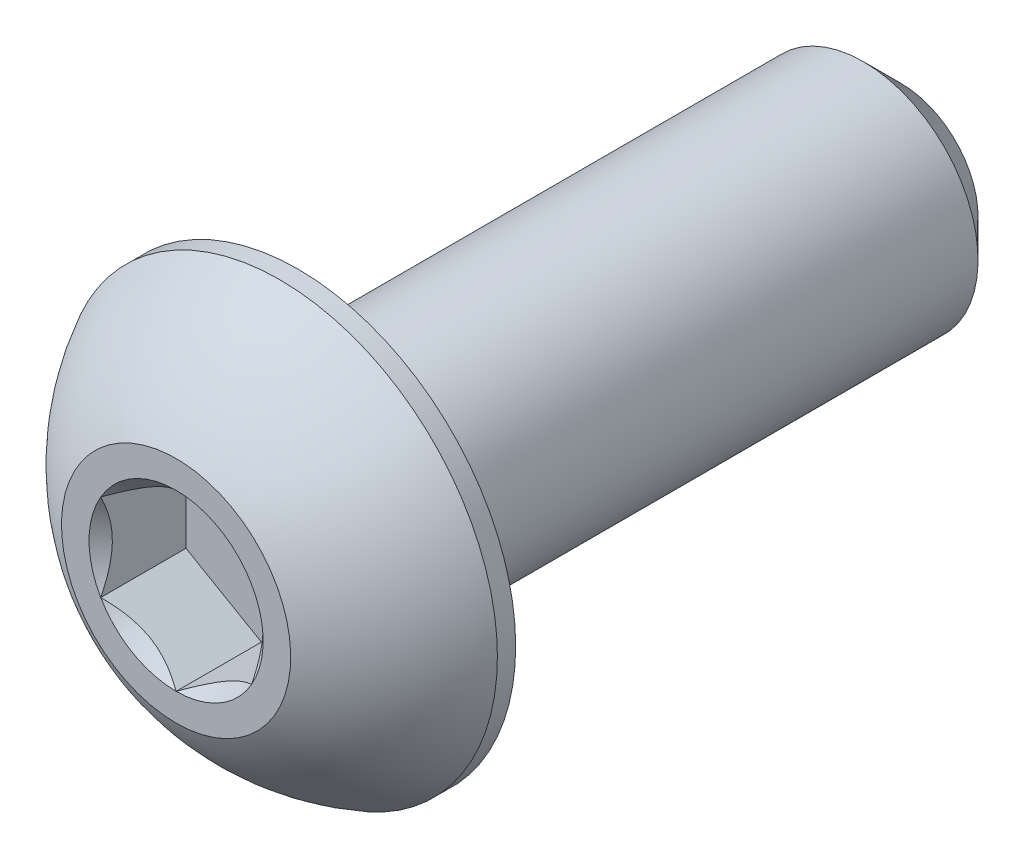
SolidWorks part; units mm, degrees
ref_plane "Front" through (0, 0, 0) normal (0, 0, 1) x (1, 0, 0)
ref_plane "Top" through (0, 0, 0) normal (0, 1, 0) x (1, 0, 0)
ref_plane "Right" through (0, 0, 0) normal (1, 0, 0) x (0, 0, -1)
sketch "Sketch1" plane through (0, 0, 0) normal (1, 0, 0) x (0, 0, -1)
  line L2 (2.5654, 2.413) -> (15.2654, 2.413)
  line L3 (15.2654, 2.413) -> (15.2654, 0)
  line L4 (15.2654, 0) -> (2.5654, 0)
  line L6 (2.1806, 4.5847) -> (2.5654, 4.5847) construction
  line L7 (15.2654, 2.413) -> (15.2654, -2.413) construction
  line L8 (0, 0) -> (2.5654, 0) construction
  line L9 (2.5654, 4.5847) -> (2.5654, -4.5847) construction
  line L11 (2.5654, 2.413) -> (2.5654, 0)
  line L13 (0, 1.5875) -> (0, -1.5875) construction
  line L14 (0, 1.5875) -> (0, 2.413) construction
  arc A3 (0, 2.413) -> (2.1806, 4.5847) centre (4.5749, 0) cw construction
  dimension "D1" = 0.3848
revolve "Revolve1" add sketch "Sketch1" angle 360 mid plane about L4
sketch "Sketch3" plane through (0, 0, -15.2654) normal (0, 0, -1) x (-1, 0, 0)
  circle A0 centre (0, 0) radius 2.413
curve "Helix/Spiral1" pitch 1.0583 height 13.7583 turns 13
sketch "Sketch2" plane through (0, 0, 0) normal (1, 0, 0) x (0, 0, -1)
  line L0 (15.2654, 2.413) -> (16.1914, 2.413)
  line L1 (16.1914, 2.413) -> (15.7946, 1.7256)
  line L2 (15.7946, 1.7256) -> (15.6623, 1.7256)
  line L3 (15.6623, 1.7256) -> (15.2654, 2.413)
  line L4 (15.4638, 2.0693) -> (15.993, 2.0693) construction
  dimension "D1" = 60
  dimension "D2" = 0.1323
  dimension "D3" = 0.5292
chamfer "Chamfer1" distance 0.7937 angle 45 1 edges at (0, 2.413, -15.2654)
sweep "Cut-Sweep1" [suppressed] cut profiles "Sketch2" path "Helix/Spiral1"
sketch "Sketch7" plane through (0, 0, 0) normal (1, 0, 0) x (0, 0, -1)
  line L6 (2.1806, 4.5847) -> (2.5654, 4.5847) construction
  line L8 (0, 0) -> (2.5654, 0) construction
  line L11 (2.5654, 4.5847) -> (2.5654, -4.5847) construction
  line L12 (2.1806, 4.5847) -> (2.5654, 4.5847)
  line L13 (0, 0) -> (2.5654, 0)
  line L14 (0, 1.5875) -> (0, -1.5875) construction
  line L15 (2.5654, 4.5847) -> (2.5654, 0)
  line L16 (0, 2.413) -> (0, 0)
  arc A2 (2.1806, 4.5847) -> (0, 2.413) centre (4.5749, 0) ccw construction
  arc A3 (2.1806, 4.5847) -> (0, 2.413) centre (4.5749, 0) ccw
revolve "Revolve2" add sketch "Sketch7" angle 360 mid plane about L13
sketch "Sketch5" plane through (0, 0, 0) normal (0, 0, 1) x (1, 0, 0)
  line L1 (1.5875, -0.9165) -> (1.5875, 0.9165)
  line L2 (1.5875, 0.9165) -> (0, 1.8331)
  line L3 (0, 1.8331) -> (-1.5875, 0.9165)
  line L4 (-1.5875, 0.9165) -> (-1.5875, -0.9165)
  line L5 (-1.5875, -0.9165) -> (0, -1.8331)
  line L6 (0, -1.8331) -> (1.5875, -0.9165)
  circle A0 centre (0, 0) radius 1.5875 construction
extrude "Cut-Extrude2" cut sketch "Sketch5" against normal blind 1.7958
sketch "Sketch6" plane through (0, 0, 0) normal (0, 0, 1) x (1, 0, 0)
  circle A0 centre (0, 0) radius 1.8331
extrude "Cut-Extrude3" cut sketch "Sketch6" against normal blind 1.7958 draft 45
sketch "Sketch9" [suppressed] plane through (0, 0, -5.0546) normal (0, 0, 1) x (1, 0, 0)
  circle A2 centre (0, 0) radius 4.7625
extrude "Boss-Extrude2" [suppressed] add sketch "Sketch9" against normal offset from surface (12.7 mm away) 31.75 up to face at (0, 1.6193, -15.2654)
sketch "Sketch10" plane through (0, 0, 0) normal (1, 0, 0) x (0, 0, -1)
  line L0 (15.2654, 2.413) -> (15.2654, -2.413) construction
  point P0 (13.6779, -2.413)
  dimension "D1" = 1.5875
equation "\"D3@Helix/Spiral1\" = \"Lg@Sketch1\" + \"D4@Helix/Spiral1\""
equation "\"D2@Sketch2\" = \"D4@Helix/Spiral1\" * .125"
equation "\"D3@Sketch2\" = \"D4@Helix/Spiral1\" * .5"
equation "\"D1@Chamfer1\" = \"D4@Helix/Spiral1\" * .75"
equation "\"D1@Cut-Extrude2\" = \"Head Ht@Sketch1\" * .7"
equation "\"D1@Sketch1\" = \"Head Ht@Sketch1\" * .15"
equation "\"D1@Sketch10\" = \"D4@Helix/Spiral1\" * 1.5"
equation "\"D1@Cut-Extrude3\" = \"D1@Cut-Extrude2\""
